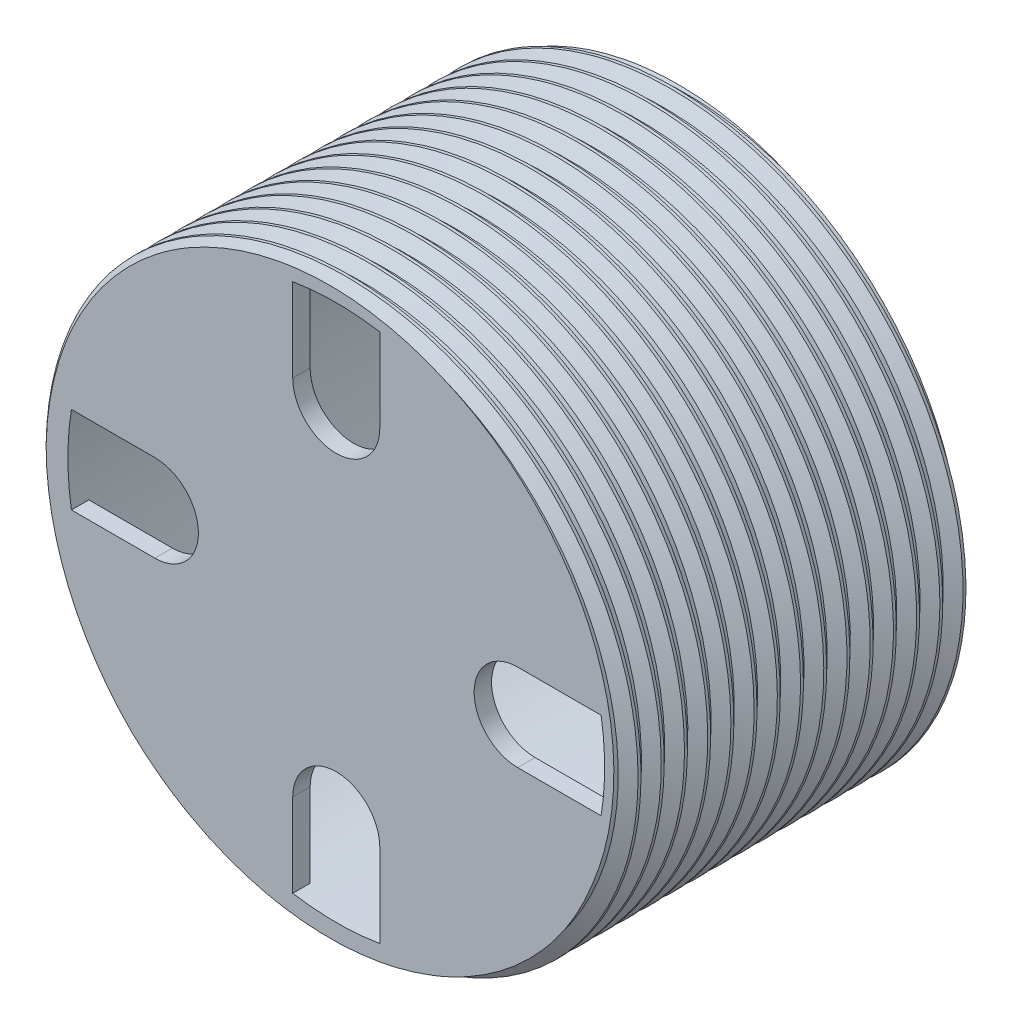
SolidWorks part; units mm, degrees
ref_plane "Plan de face" through (0, 0, 0) normal (0, 0, 1) x (1, 0, 0)
ref_plane "Plan de dessus" through (0, 0, 0) normal (0, 1, 0) x (1, 0, 0)
ref_plane "Plan de droite" through (0, 0, 0) normal (1, 0, 0) x (0, 0, -1)
sketch "Esquisse1" plane through (0, 0, 0) normal (0, 0, 1) x (1, 0, 0)
  circle A2 centre (-150, 595) radius 44.5 construction
  circle A3 centre (-150, 595) radius 46.25
  circle A8 centre (-150, 595) radius 50
  dimension "D3" = 100
  dimension "D2" = 92.5
extrude "Boss.-Extru.1" add sketch "Esquisse1" along normal blind 57
extrude "Boss.-Extru.2" add sketch "Esquisse1<2>" along normal blind 3 from surface contours A8 starting at face at (-100, 595, 57)
sketch "Esquisse1<2>" plane through (0, 0, 0) normal (0, 0, 1) x (1, 0, 0) same geometry as "Esquisse1"
thread "Filetage1" pitch 4 method cut trim with start face yes trim with end face yes profile "Profil de filetage1" start angle 0, offset 3.5, length 63.5, pitch 4, diameter 100
ref_plane "Plan1" through (-200, 595, 63.5) normal (0, -1, 0) x (-1, 0, 0)
sketch "Profil de filetage1" plane through (-200, 595, 63.5) normal (0, -1, 0) x (-1, 0, 0)
  line L0 (0, 0) -> (0, 4) construction
  line L11 (0, 0) -> (0, 3.5)
  line L12 (0, 3.5) -> (-2.1651, 2.25)
  line L13 (-2.1651, 2.25) -> (-2.1651, 1.25)
  line L15 (-2.1651, 1.25) -> (0, 0)
  line L17 (-2.1651, 1.75) -> (0, 1.75) construction
  point P2 (0, 0)
  dimension "Pitch" = 4
  dimension "Profile_Angle" = 60
  dimension "Profile_Land" = 1
  dimension "Profile_Height" = 2.1651
sketch "Esquisse5" plane through (0, 0, 60) normal (0, 0, 1) x (1, 0, 0)
  line L0 (-196.25, 595) -> (-103.75, 595) construction
  line L1 (-196.25, 602.5) -> (-196.25, 587.5) construction
  line L2 (-195.6378, 602.5) -> (-181.25, 602.5)
  line L3 (-195.6378, 587.5) -> (-181.25, 587.5)
  line L4 (-196.25, 602.5) -> (-195.6378, 602.5) construction
  line L5 (-196.25, 587.5) -> (-195.6378, 587.5) construction
  line L6 (-142.5, 640.6378) -> (-142.5, 626.25)
  line L7 (-157.5, 640.6378) -> (-157.5, 626.25)
  line L8 (-104.3622, 587.5) -> (-118.75, 587.5)
  line L9 (-104.3622, 602.5) -> (-118.75, 602.5)
  line L10 (-157.5, 549.3622) -> (-157.5, 563.75)
  line L11 (-142.5, 549.3622) -> (-142.5, 563.75)
  arc A0 (-181.25, 602.5) -> (-181.25, 587.5) centre (-181.25, 595) cw
  circle A1 centre (-150, 595) radius 46.25
  circle A2 centre (-150, 595) radius 46.25
  arc A3 (-142.5, 626.25) -> (-157.5, 626.25) centre (-150, 626.25) cw
  arc A4 (-118.75, 587.5) -> (-118.75, 602.5) centre (-118.75, 595) cw
  arc A5 (-157.5, 563.75) -> (-142.5, 563.75) centre (-150, 563.75) cw
  point P8 (-196.25, 595)
  point P31 (-150, 595)
  dimension "D2" = 15
  dimension "D3" = 15
  dimension "D1" = 0
  dimension "D4" = 4
extrude "Enlèv. mat.-Extru.1" cut sketch "Esquisse5" against normal up to surface (3 mm away) contours L2 A2 L3 A0 | A3 L6 A2 L7 | A4 L8 A2 L9 | A5 L10 A2 L11 region at (-185.6361, 595, 60) region at (-150, 630.6361, 60) region at (-150, 559.3639, 60) region at (-114.3639, 595, 60) up to face at (-103.75, 595, 57)
scale "Echelle1" bodies to scale 104 scale about origin uniform scaling yes scale factor 0.5
